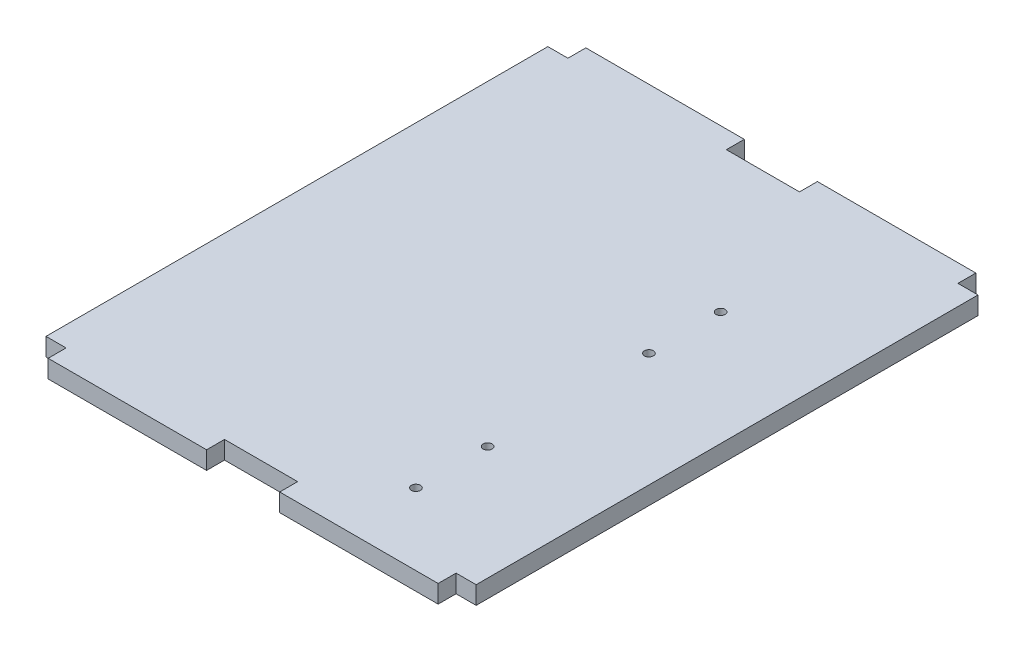
SolidWorks part; units mm, degrees
ref_plane "Front Plane" through (0, 0, 0) normal (0, 0, 1) x (1, 0, 0)
ref_plane "Top Plane" through (0, 0, 0) normal (0, 1, 0) x (1, 0, 0)
ref_plane "Right Plane" through (0, 0, 0) normal (1, 0, 0) x (0, 0, -1)
sketch "Sketch1" plane through (0, 0, 0) normal (0, 1, 0) x (1, 0, 0)
  line L1 (0, 0) -> (304.8, 0)
  line L2 (0, 0) -> (0, 355.6)
  line L3 (0, 355.6) -> (304.8, 355.6)
  line L4 (304.8, 0) -> (304.8, 355.6)
  dimension "D1" = 355.6
  dimension "D2" = 304.8
extrude "Boss-Extrude1" add sketch "Sketch1" along normal blind 12.7
sketch "Sketch2" plane through (0, 0, 0) normal (0, -1, 0) x (1, 0, 0)
  line L0 (0, 0) -> (304.8, 0) construction
  line L1 (0, -355.6) -> (0, 0) construction
  circle A0 centre (224.028, -38.1) radius 3.175
  circle A1 centre (224.028, -88.9) radius 3.175
  circle A2 centre (224.028, -203.2) radius 3.175
  circle A3 centre (224.028, -254) radius 3.175
  dimension "D3" = 88.9
  dimension "D6" = 6.35
  dimension "D1" = 38.1
  dimension "D2" = 224.028
  dimension "D4" = 203.2
  dimension "D5" = 254
  dimension "D7" = 224.028
  dimension "D8" = 224.028
  dimension "D9" = 224.028
extrude "Cut-Extrude1" cut sketch "Sketch2" against normal blind 12.7
sketch "Sketch3" plane through (0, 12.7, 0) normal (0, 1, 0) x (1, 0, 0)
  line L0 (152.4, 355.6) -> (152.4, 250.206) construction
  line L1 (0, 177.8) -> (22.2548, 177.8) construction
  line L2 (14.224, 355.6) -> (126.492, 355.6)
  line L3 (14.224, 355.6) -> (14.224, 368.3)
  line L4 (0, 355.6) -> (0, 0)
  line L5 (0, 0) -> (304.8, 0)
  line L6 (304.8, 0) -> (304.8, 355.6)
  line L7 (304.8, 355.6) -> (0, 355.6)
  line L8 (0, 355.6) -> (0, 0) construction
  line L9 (0, 0) -> (304.8, 0) construction
  line L10 (304.8, 0) -> (304.8, 355.6) construction
  line L11 (304.8, 355.6) -> (0, 355.6) construction
  line L12 (14.224, 368.3) -> (126.492, 368.3)
  line L13 (126.492, 355.6) -> (126.492, 368.3)
  line L14 (290.576, 368.3) -> (178.308, 368.3)
  line L15 (178.308, 355.6) -> (178.308, 368.3)
  line L16 (290.576, 355.6) -> (178.308, 355.6)
  line L17 (290.576, 355.6) -> (290.576, 368.3)
  line L18 (290.576, 0) -> (290.576, -12.7)
  line L19 (290.576, 0) -> (178.308, 0)
  line L20 (178.308, 0) -> (178.308, -12.7)
  line L21 (290.576, -12.7) -> (178.308, -12.7)
  line L22 (14.224, -12.7) -> (126.492, -12.7)
  line L23 (126.492, 0) -> (126.492, -12.7)
  line L24 (14.224, 0) -> (126.492, 0)
  line L25 (14.224, 0) -> (14.224, -12.7)
  point P24 (190.5, 250.206)
  dimension "D2" = 25.908
  dimension "D3" = 112.268
  dimension "D4" = 12.7
  dimension "D1" = 0
extrude "Boss-Extrude2" add sketch "Sketch3" against normal blind 12.7
